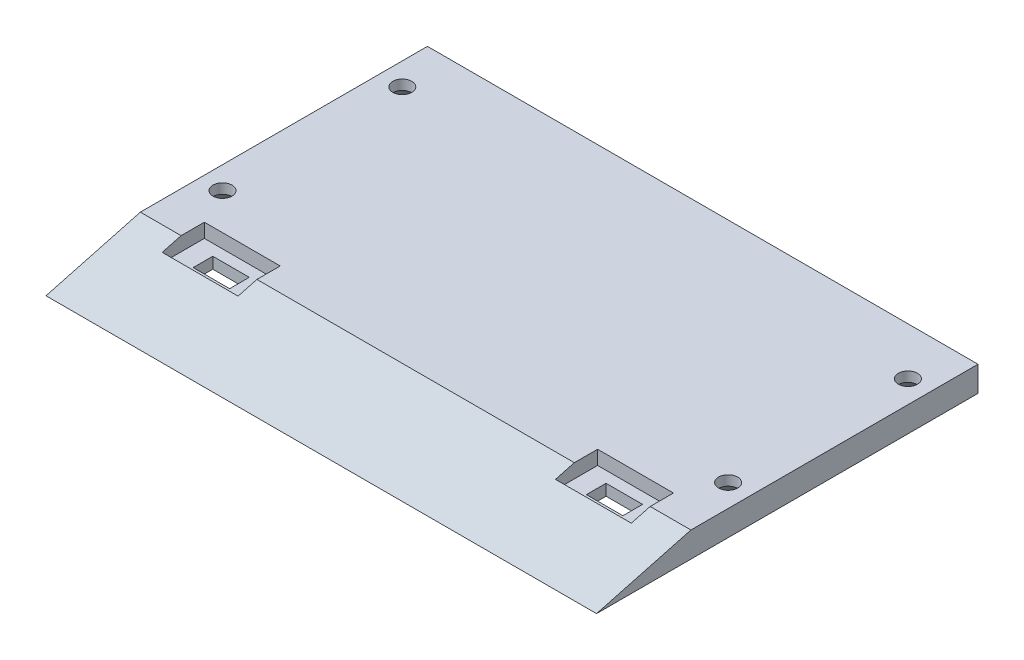
SolidWorks part; units mm, degrees
material "Stainless Steel (ferritic)"
ref_plane "Front Plane" through (0, 0, 0) normal (0, 0, 1) x (1, 0, 0)
ref_plane "Top Plane" through (0, 0, 0) normal (0, 1, 0) x (1, 0, 0)
ref_plane "Right Plane" through (0, 0, 0) normal (1, 0, 0) x (0, 0, -1)
sketch "Croquis1" plane through (0, 0, 0) normal (1, 0, 0) x (0, 0, -1)
  line L0 (0, 0) -> (67.9, 0)
  line L2 (16.7942, 4.5) -> (0, 0)
  line L3 (16.7942, 4.5) -> (67.9, 4.5)
  line L4 (67.9, 4.5) -> (67.9, 0)
  dimension "D1" = 15
  dimension "D2" = 67.9
  dimension "D3" = 4.5
  dimension "D4" = 51.1058
extrude "Saliente-Extruir1" add sketch "Croquis1" along normal blind 100
sketch "Croquis2" plane through (0, 0, 0) normal (0, -1, 0) x (1, 0, 0)
  point P7 (95, -59.42)
  point P18 (5, -59.42)
  point P19 (5, -27.42)
  point P20 (95, -27.42)
  dimension "D1" = 2
  dimension "D3" = 32
  dimension "D2" = 2
hole_wizard "CSK for M3 Flat Head Machine Screw1" positions "Croquis2" profile "Croquis3" countersink size "M3" standard "ANSI Metric" end condition through all
sketch "Croquis3" plane through (95, 0, -59.42) normal (1, 0, 0) x (0, 0, -1)
  line L0 (0, 0) -> (0, 4.5)
  line L1 (0, 4.5) -> (1.7, 4.5)
  line L2 (1.7, 4.5) -> (1.7, 2.741)
  line L3 (1.7, 2.741) -> (4, 0)
  line L5 (4, 0) -> (0, 0)
  line L6 (-1.7, 2.741) -> (-4, 0) construction
  line L11 (0, -6.35) -> (0, 107.95) construction
  dimension "Thru Hole Dia." = 3.4
  dimension "Thru Hole Depth" = 4.5
  dimension "Near C'Sink Dia." = 8
  dimension "Near C'Sink Angle" = 80
sketch "Croquis4" plane through (0, 4.5, 0) normal (0, 1, 0) x (1, 0, 0)
  line L1 (11.75, 18.94) -> (18.25, 18.94)
  line L2 (11.75, 18.94) -> (11.75, 15.44)
  line L3 (11.75, 15.44) -> (18.25, 15.44)
  line L4 (18.25, 18.94) -> (18.25, 15.44)
  line L10 (81.75, 18.94) -> (88.25, 18.94)
  line L11 (81.75, 18.94) -> (81.75, 15.44)
  line L15 (81.75, 15.44) -> (88.25, 15.44)
  line L16 (88.25, 18.94) -> (88.25, 15.44)
  point P0 (15, 17.19)
  point P4 (85, 17.19)
extrude "Cortar-Extruir3" cut sketch "Croquis4" against normal through all
sketch "Croquis8" plane through (0, 4.5, 0) normal (0, 1, 0) x (1, 0, 0)
  line L1 (8.25, 20.94) -> (21.75, 20.94)
  line L2 (8.25, 20.94) -> (8.25, 13.44)
  line L3 (8.25, 13.44) -> (21.75, 13.44)
  line L4 (21.75, 20.94) -> (21.75, 13.44)
  line L5 (8.25, 20.94) -> (21.75, 13.44) construction
  line L6 (8.25, 13.44) -> (21.75, 20.94) construction
  line L7 (78.25, 20.94) -> (91.75, 20.94)
  line L8 (78.25, 20.94) -> (78.25, 13.44)
  line L9 (78.25, 13.44) -> (91.75, 13.44)
  line L10 (91.75, 20.94) -> (91.75, 13.44)
  point P0 (15, 17.19)
  point P5 (87.6503, 17.19)
extrude "Cortar-Extruir4" cut sketch "Croquis8" against normal blind 2.5
sketch "Croquis11" plane through (100, 0, 0) normal (1, 0, 0) x (0, 0, -1)
  line L0 (0, 0) -> (67.9, 0)
  line L1 (67.9, 0) -> (67.9, 7.3402)
  line L2 (67.9, 7.3402) -> (-0.4555, 7.3402)
  line L3 (-0.4555, 7.3402) -> (0, 0)
extrude "Cortar-Extruir5" cut sketch "Croquis11" against normal blind 1
sketch "Croquis12" plane through (0, 0, 0) normal (-1, 0, 0) x (0, 0, 1)
  line L0 (-67.9, 0) -> (0, 0)
  line L1 (0, 0) -> (0, 8.5292)
  line L2 (0, 8.5292) -> (-67.9, 8.5292)
  line L3 (-67.9, 8.5292) -> (-67.9, 0)
extrude "Cortar-Extruir6" cut sketch "Croquis12" against normal blind 1
